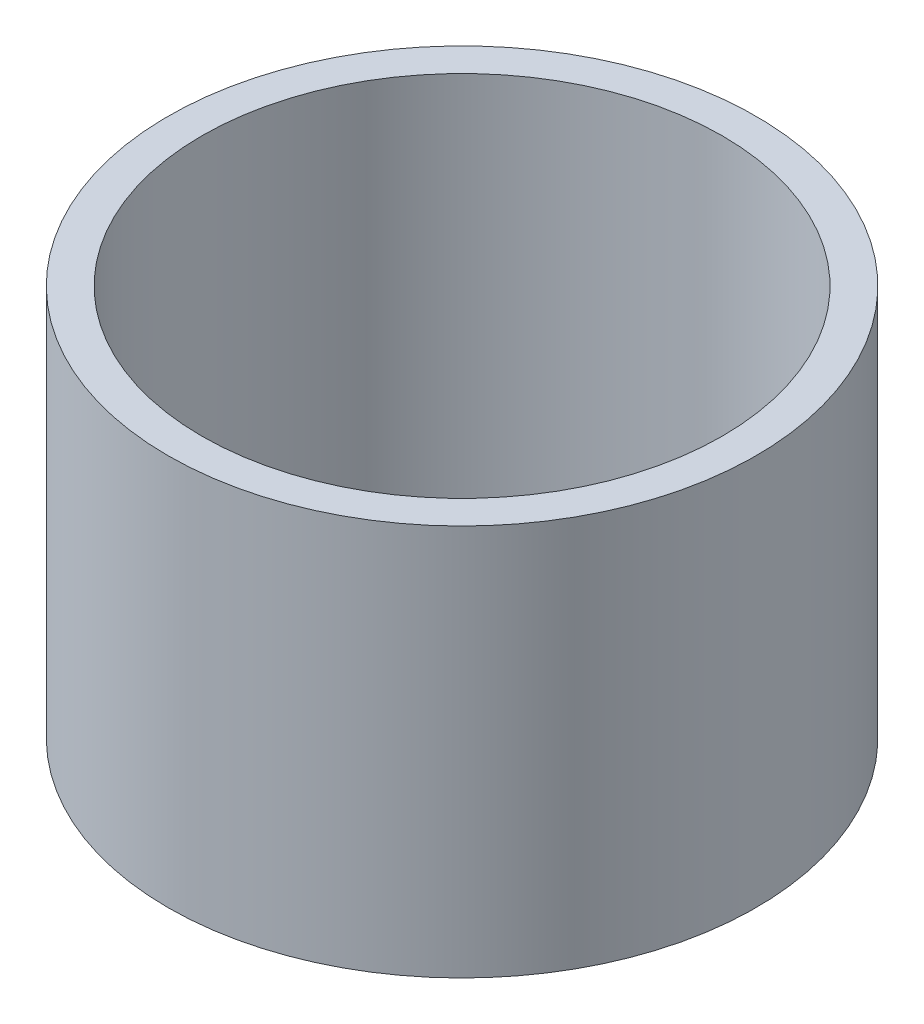
SolidWorks part; units mm, degrees
ref_plane "Front Plane" through (0, 0, 0) normal (0, 0, 1) x (1, 0, 0)
ref_plane "Top Plane" through (0, 0, 0) normal (0, 1, 0) x (1, 0, 0)
ref_plane "Right Plane" through (0, 0, 0) normal (1, 0, 0) x (0, 0, -1)
sketch "Sketch1" plane through (0, 0, 0) normal (0, 1, 0) x (1, 0, 0)
  circle A0 centre (0, 0) radius 57.5
  dimension "SLEEVE_OD" = 115
extrude "Boss-Extrude1" add sketch "Sketch1" along normal blind 76.5517
sketch "Sketch2" plane through (0, 0, 0) normal (0, 1, 0) x (1, 0, 0)
  circle A0 centre (0, 0) radius 50.8881
  dimension "BORE_D" = 101.7761
extrude "Cut-Extrude1" cut sketch "Sketch2" along normal through all
chamfer "Chamfer1" distance 3.6526 angle 60 rebuild error yes
